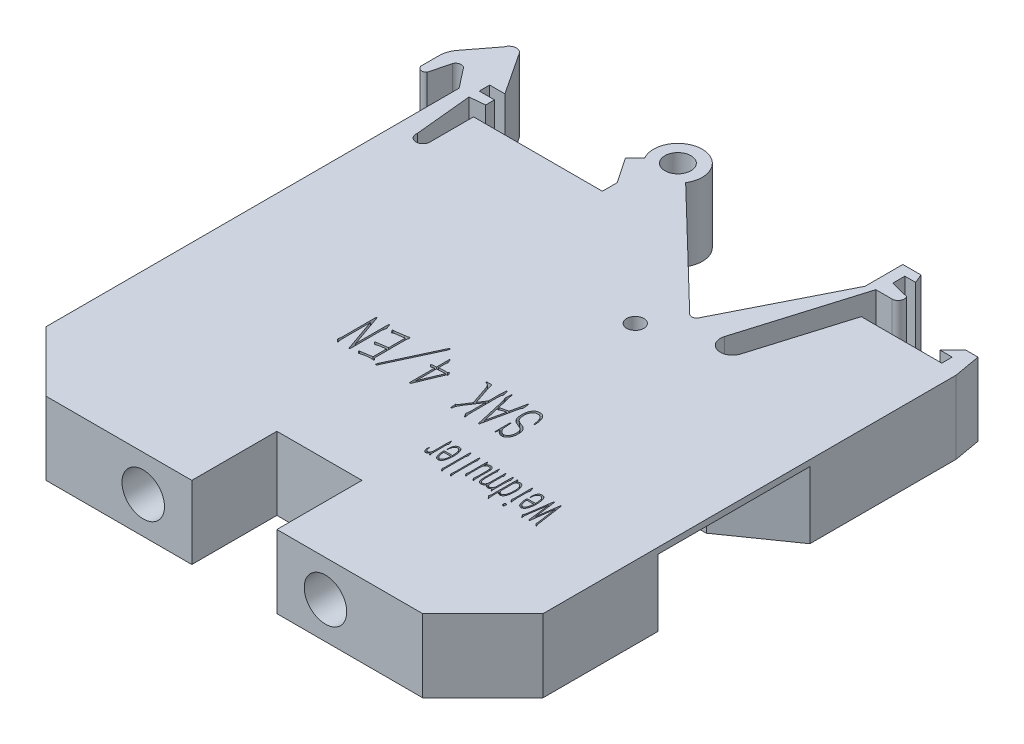
SolidWorks part; units mm, degrees
ref_plane "前视基准面" through (0, 0, 0) normal (0, 0, 1) x (1, 0, 0)
ref_plane "上视基准面" through (0, 0, 0) normal (0, 1, 0) x (1, 0, 0)
ref_plane "右视基准面" through (0, 0, 0) normal (1, 0, 0) x (0, 0, -1)
sketch "草图1" plane through (0, 0, 0) normal (0, 1, 0) x (1, 0, 0)
  line L0 (-61.5074, 0) -> (61.1732, 0) construction
  line L1 (0, 0) -> (0, 95.9382) construction
  line L2 (-3.5, 7) -> (3.5, 7)
  line L3 (3.5, 7) -> (3.5, 0)
  line L4 (3.5, 0) -> (15.5, 0)
  line L5 (15.5, 0) -> (20.4497, 4.9497)
  line L6 (20.4497, 4.9497) -> (20.4497, 38.9497)
  line L7 (-20.4497, 4.9497) -> (-20.4497, 38.9497)
  line L8 (-15.5, 0) -> (-20.4497, 4.9497)
  line L9 (-3.5, 0) -> (-15.5, 0)
  line L10 (-3.5, 7) -> (-3.5, 0)
  line L11 (20.4497, 38.9497) -> (20.0647, 41.1333)
  line L12 (20.0647, 41.1333) -> (19.0647, 41.1333)
  line L13 (19.0647, 41.1333) -> (18.0041, 40.0726)
  line L14 (18.0041, 40.0726) -> (19.0041, 40.0726)
  line L15 (19.0041, 40.0726) -> (19.0041, 39.2126)
  line L16 (-18.9543, 34.0334) -> (-19.4188, 38.7245)
  line L17 (12.3799, 39.2126) -> (10.0805, 31.5855)
  line L18 (8.1656, 32.1627) -> (11.052, 41.7371)
  line L19 (11.052, 41.7371) -> (12.3896, 41.7371)
  line L20 (12.8059, 42.514) -> (11.2867, 42.8929)
  line L21 (11.2867, 42.8929) -> (11.2867, 43.8921)
  line L22 (11.2867, 43.8921) -> (12.1702, 43.8921)
  line L23 (12.1702, 43.8921) -> (11.8608, 44.6446)
  line L24 (11.8608, 44.6446) -> (10.3682, 44.6446)
  line L25 (10.3682, 44.6446) -> (10.3682, 41.5389)
  line L26 (10.3682, 41.5389) -> (5.7821, 32.4476)
  line L27 (5.1289, 32.344) -> (-4.3994, 41.5389)
  line L28 (-7.833, 41.5907) -> (-8.6206, 40.803)
  line L29 (-8.6206, 40.803) -> (-7.2128, 38.7245)
  line L30 (-7.2128, 38.7245) -> (-7.2128, 37.4978)
  line L31 (-7.2128, 37.4978) -> (-17.8128, 37.4978)
  line L32 (-17.8128, 37.4978) -> (-17.8128, 33.9126)
  line L33 (-19.4188, 38.7245) -> (-18.1635, 38.8488)
  line L35 (-18.1635, 38.8488) -> (-18.1635, 39.5726)
  line L36 (-18.1635, 39.5726) -> (-19.4188, 39.5726)
  line L37 (-19.4188, 39.5726) -> (-19.4188, 40.429)
  line L38 (-19.4188, 40.429) -> (-18.1635, 40.429)
  line L39 (-18.1635, 40.429) -> (-20.4497, 43.8921)
  line L40 (-21.5551, 43.7351) -> (-23.2038, 41.5907)
  line L41 (-23.5988, 40.429) -> (-23.5988, 38.9497)
  line L42 (-22.9, 38.7733) -> (-22.4849, 40.429)
  line L43 (-21.639, 40.4666) -> (-20.4497, 38.9497)
  line L45 (19.0041, 39.2126) -> (12.3799, 39.2126)
  arc A0 (10.0805, 31.5855) -> (8.1656, 32.1627) centre (9.123, 31.8741) cw
  arc A1 (12.3896, 41.7371) -> (12.8059, 42.514) centre (12.3896, 42.2371) ccw
  arc A2 (5.7821, 32.4476) -> (5.1289, 32.344) centre (5.4182, 32.6311) cw
  arc A3 (-4.3994, 41.5389) -> (-7.833, 41.5907) centre (-6.1005, 42.6013) ccw
  arc A4 (-17.8128, 33.9126) -> (-18.9543, 34.0334) centre (-18.3899, 33.9126) cw
  arc A5 (-20.4497, 43.8921) -> (-21.5551, 43.7351) centre (-20.9652, 43.5517) ccw
  arc A6 (-23.2038, 41.5907) -> (-23.5988, 40.429) centre (-21.6929, 40.429) ccw
  arc A7 (-23.5988, 38.9497) -> (-22.9, 38.7733) centre (-23.2038, 39.0421) ccw
  arc A8 (-22.4849, 40.429) -> (-21.639, 40.4666) centre (-22.0534, 40.2546) cw
  point P16 (0, 7)
  dimension "D8" = 0.5
  dimension "D9" = 0.86
  dimension "D1" = 7
  dimension "D2" = 7
  dimension "D3" = 12
  dimension "D4" = 7
  dimension "D5" = 135
  dimension "D6" = 34
  dimension "D7" = 10.6
  dimension "D10" = 1
  dimension "D11" = 1.5
  dimension "D12" = 1
extrude "凸台-拉伸1" add sketch "草图1" along normal blind 6
sketch "草图2" plane through (0, 0, 0) normal (0, 0, 1) x (1, 0, 0)
  line L0 (-3.5, 6) -> (-3.5, 0) construction
  line L1 (3.5, 6) -> (3.5, 0) construction
  circle A0 centre (-7.5, 3) radius 1.75
  circle A1 centre (7.5, 3) radius 1.75
  point P6 (-3.5, 3)
  point P7 (3.5, 3)
  dimension "D1" = 3.5
  dimension "D2" = 4
  dimension "D3" = 4
extrude "切除-拉伸1" cut sketch "草图2" against normal blind 5
sketch "草图3" plane through (0, 0, -5) normal (0, 0, 1) x (1, 0, 0)
  line L1 (-7.75, 1.5875) -> (-7.25, 1.5875)
  line L2 (-7.75, 1.5875) -> (-7.75, 4.4125)
  line L3 (-7.75, 4.4125) -> (-7.25, 4.4125)
  line L4 (-7.25, 1.5875) -> (-7.25, 4.4125)
  line L5 (-7.75, 1.5875) -> (-7.25, 4.4125) construction
  line L6 (-7.75, 4.4125) -> (-7.25, 1.5875) construction
  line L7 (7.25, 1.5875) -> (7.75, 1.5875)
  line L8 (7.25, 1.5875) -> (7.25, 4.4125)
  line L9 (7.25, 4.4125) -> (7.75, 4.4125)
  line L10 (7.75, 1.5875) -> (7.75, 4.4125)
  line L11 (7.25, 1.5875) -> (7.75, 4.4125) construction
  line L12 (7.25, 4.4125) -> (7.75, 1.5875) construction
  point P0 (-7.5, 3)
  point P6 (7.5, 3)
  dimension "D1" = 0.5
extrude "切除-拉伸2" cut sketch "草图3" against normal blind 1
sketch "草图4" plane through (0, 6, 0) normal (0, 1, 0) x (1, 0, 0)
  circle A0 centre (-6.1005, 42.6013) radius 1.0746
  arc A1 (-4.3994, 41.5389) -> (-7.833, 41.5907) centre (-6.1005, 42.6013) ccw construction
extrude "切除-拉伸3" cut sketch "草图4" against normal through all
sketch "草图5" plane through (0, 6, 0) normal (0, 1, 0) x (1, 0, 0)
  circle A0 centre (3.5586, 29.433) radius 0.7079
extrude "切除-拉伸4" cut sketch "草图5" against normal through all
sketch "草图6" plane through (-20.4497, 0, 0) normal (-1, 0, 0) x (0, 0, 1)
  line L0 (-38.9497, 0) -> (-4.9497, 0) construction
  line L1 (-26.9151, 5.5) -> (-14.4151, 5.5)
  line L2 (-26.9151, 5.5) -> (-26.9151, 0)
  line L3 (-26.9151, 0) -> (-14.4151, 0)
  line L4 (-14.4151, 5.5) -> (-14.4151, 0)
  line L5 (-26.9151, 5.5) -> (-14.4151, 0) construction
  line L6 (-26.9151, 0) -> (-14.4151, 5.5) construction
  point P0 (-20.6651, 2.75)
  dimension "D1" = 12.5
  dimension "D2" = 5.5
extrude "切除-拉伸5" cut sketch "草图6" against normal blind 5
sketch "草图7" plane through (0, 5.5, 0) normal (0, -1, 0) x (1, 0, 0)
  line L0 (-20.4497, -26.9151) -> (-15.4497, -26.9151)
  line L2 (-15.4497, -26.9151) -> (-15.4497, -23.4151)
  line L4 (-15.4497, -14.4151) -> (-15.4497, -26.9151) construction
  line L5 (-15.4497, -23.4151) -> (-20.4497, -26.9151)
  line L6 (-20.4497, -14.4151) -> (-15.4497, -14.4151)
  line L7 (-15.4497, -14.4151) -> (-15.4497, -17.9151)
  line L8 (-15.4497, -17.9151) -> (-20.4497, -14.4151)
  dimension "D1" = 3.5
  dimension "D2" = 3.5
extrude "凸台-拉伸2" add sketch "草图7" along normal up to surface (5.5 mm away) up to face at (-3.8878, 0, -32.9886)
sketch "草图8" plane through (-15.4497, 0, 0) normal (-1, 0, 0) x (0, 0, 1)
  line L0 (-17.9151, 0) -> (-17.9151, 5.5) construction
  line L1 (-23.3973, 0) -> (-17.9151, 0)
  line L2 (-23.3973, 0) -> (-23.3973, 4.6608)
  line L3 (-23.3973, 4.6608) -> (-17.9151, 4.6608)
  line L4 (-17.9151, 0) -> (-17.9151, 4.6608)
  line L5 (-23.3973, 0) -> (-17.9151, 4.6608) construction
  line L6 (-23.3973, 4.6608) -> (-17.9151, 0) construction
  point P0 (-20.6562, 2.3304)
extrude "切除-拉伸6" cut sketch "草图8" against normal blind 10
mirror "镜向1" about plane through (0, 0, 0) normal (1, 0, 0) of "切除-拉伸5", "凸台-拉伸2", "切除-拉伸6"
sketch "草图9" plane through (0, 6, 0) normal (0, 1, 0) x (1, 0, 0)
  line L0 (13.9859, 13.5861) -> (-4.0177, 13.5861) construction
  line L1 (9.6403, 19.4492) -> (-10.5878, 19.4492) construction
  text T0 "Weidmuller" font "汉仪长仿宋体" height in points 10
  text T1 "SAK 4/EN"
extrude "切除-拉伸7" cut sketch "草图9" against normal blind 1
sketch "草图10" plane through (5.4497, 0, 0) normal (1, 0, 0) x (0, 0, -1)
  line L0 (23.3973, 0) -> (17.9151, 0) construction
  line L1 (23.3973, 4.6608) -> (23.3973, 0) construction
  point P0 (20.6562, 2.3304)
  point P3 (20.6562, 0)
  point P6 (23.3973, 2.3304)
sketch "0_1_Point" plane through (-5.4497, 0, 0) normal (-1, 0, 0) x (0, 0, 1)
  point P0 (-20.6562, 2.3304)
sketch "0_0_Point" plane through (5.4497, 0, 0) normal (1, 0, 0) x (0, 0, -1)
  point P0 (20.6562, 2.3304)
other "0_0" parameters "直径"=2, "端头长度"=2
ref_axis "基准轴1" through (15.4497, 2.3304, -20.6562) along (-1, 0, 0)
other "0_1" parameters "直径"=2, "端头长度"=2
ref_axis "基准轴2" through (-15.4497, 2.3304, -20.6562) along (1, 0, 0)
